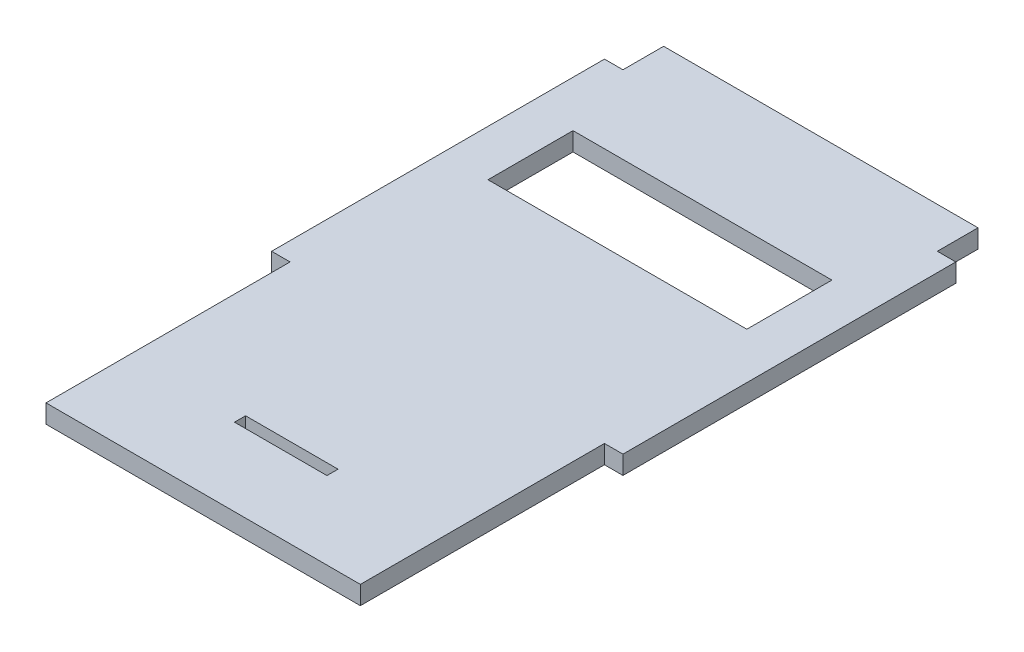
SolidWorks part; units mm, degrees
ref_plane "Alzado" through (0, 0, 0) normal (0, 0, 1) x (1, 0, 0)
ref_plane "Planta" through (0, 0, 0) normal (0, 1, 0) x (1, 0, 0)
ref_plane "Vista lateral" through (0, 0, 0) normal (1, 0, 0) x (0, 0, -1)
sketch "Croquis1" plane through (0, 0, 0) normal (0, 1, 0) x (1, 0, 0)
  line L0 (-42.5, -17.5) -> (42.5, -17.5) construction
  line L1 (-42.5, -83.5) -> (42.5, -83.5)
  line L2 (-42.5, -83.5) -> (-42.5, -17.5)
  line L3 (-42.5, 83.5) -> (42.5, 83.5)
  line L4 (42.5, -83.5) -> (42.5, -17.5)
  line L5 (-42.5, -83.5) -> (42.5, 83.5) construction
  line L6 (-42.5, 83.5) -> (42.5, -83.5) construction
  line L7 (-42.5, 72.5) -> (-42.5, 83.5)
  line L8 (-42.5, -17.5) -> (-47.5, -17.5)
  line L9 (42.5, 72.5) -> (42.5, 83.5)
  line L10 (-42.5, 72.5) -> (-47.5, 72.5)
  line L11 (-47.5, -17.5) -> (-47.5, 72.5)
  line L12 (42.5, 72.5) -> (47.5, 72.5)
  line L13 (0, 83.5) -> (0, -83.5) construction
  line L14 (42.5, -17.5) -> (47.5, -17.5)
  line L15 (47.5, 72.5) -> (47.5, -17.5)
  line L17 (-12.5, -62.5396) -> (12.5, -62.5396)
  line L18 (-12.5, -62.5396) -> (-12.5, -59.5396)
  line L19 (-12.5, -59.5396) -> (12.5, -59.5396)
  line L20 (12.5, -62.5396) -> (12.5, -59.5396)
  line L21 (-12.5, -62.5396) -> (12.5, -59.5396) construction
  line L22 (-12.5, -59.5396) -> (12.5, -62.5396) construction
  line L23 (-35, 28.5) -> (35, 28.5)
  line L24 (-35, 28.5) -> (-35, 51.5)
  line L25 (-35, 51.5) -> (35, 51.5)
  line L26 (35, 28.5) -> (35, 51.5)
  line L27 (-35, 28.5) -> (35, 51.5) construction
  line L28 (-35, 51.5) -> (35, 28.5) construction
  point P0 (0, 0)
  point P16 (0, -61.0396)
  point P21 (0, 40)
  dimension "D1" = 167
  dimension "D2" = 85
  dimension "D3" = 11
  dimension "D4" = 90
  dimension "D5" = 5
  dimension "D6" = 5
  dimension "D7" = 25
  dimension "D8" = 3
  dimension "D9" = 70
  dimension "D10" = 23
  dimension "D11" = 40
extrude "Saliente-Extruir1" add sketch "Croquis1" along normal blind 5
